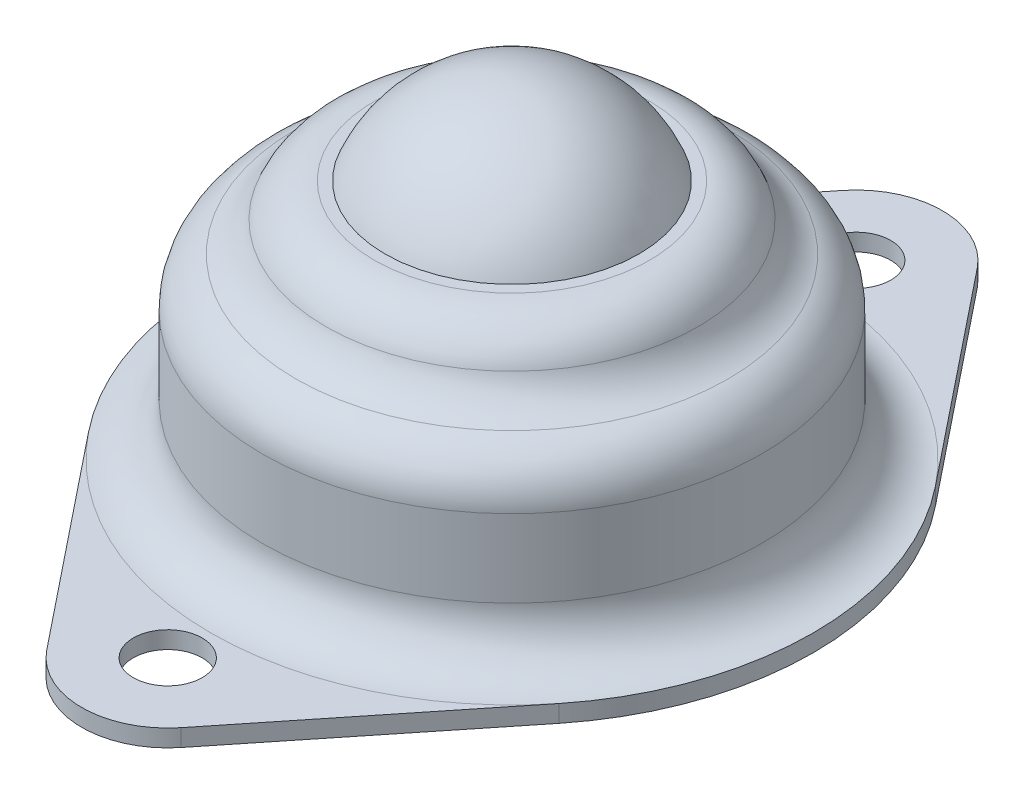
SolidWorks part; units mm, degrees
ref_plane "前视基准面" through (0, 0, 0) normal (0, 0, 1) x (1, 0, 0)
ref_plane "上视基准面" through (0, 0, 0) normal (0, 1, 0) x (1, 0, 0)
ref_plane "右视基准面" through (0, 0, 0) normal (1, 0, 0) x (0, 0, -1)
other "Configuration Table"
sketch "草图1" plane through (0, 0, 0) normal (0, 1, 0) x (1, 0, 0)
  line L0 (0, 0) -> (17.5, 0) construction
  line L1 (0, 25) -> (0, -25) construction
  line L2 (-3.9031, 23.125) -> (-13.6609, 10.9375)
  line L3 (3.9031, 23.125) -> (13.6609, 10.9375)
  line L4 (0, 0) -> (-17.5, 0) construction
  line L5 (3.9031, -23.125) -> (13.6609, -10.9375)
  line L6 (-3.9031, -23.125) -> (-13.6609, -10.9375)
  arc A1 (-13.6609, 10.9375) -> (-13.6609, -10.9375) centre (0, 0) ccw
  circle A2 centre (0, 20) radius 2
  arc A4 (3.9031, 23.125) -> (-3.9031, 23.125) centre (0, 20) ccw
  circle A6 centre (0, -20) radius 2
  arc A7 (13.6609, -10.9375) -> (13.6609, 10.9375) centre (0, 0) ccw
  arc A8 (3.9031, -23.125) -> (-3.9031, -23.125) centre (0, -20) cw
  point P15 (0, 0)
  dimension "D1" = 4
  dimension "D4" = 50
  dimension "D2" = 40
  dimension "D3" = 35
extrude "凸台-拉伸1" add sketch "草图1" along normal blind 1
sketch "草图3" plane through (0, 0, 0) normal (1, 0, 0) x (0, 0, -1)
  line L0 (0, 0) -> (0, 20) construction
  line L1 (-14.5, 1) -> (-14.5, 8.5)
  line L2 (-23.125, 1) -> (-10.9375, 1) construction
  line L5 (-8, 15) -> (0, 15)
  line L6 (0, 15) -> (0, 1)
  line L7 (10.9375, 1) -> (-10.9375, 1) construction
  line L8 (0, 1) -> (-14.5, 1)
  line L13 (-14.5, 8.5) -> (-8, 15) construction
  line L14 (0, 20) -> (0, 15)
  arc A1 (0, 20) -> (0, 4.12) centre (0, 12.06) ccw
  arc A2 (-14.5, 8.5) -> (-12.5575, 11.3075) centre (-11.5, 8.5) cw
  arc A3 (-12.5575, 11.3075) -> (-10.8075, 13.0575) centre (-13.6149, 14.1149) ccw
  arc A4 (-10.8075, 13.0575) -> (-8, 15) centre (-8, 12) cw
  dimension "D4" = 15.88
  dimension "D5" = 3
  dimension "D1" = 20
  dimension "D2" = 29
  dimension "D3" = 5
  dimension "D6" = 45
  dimension "D7" = 16
revolve "旋转2" add sketch "草图3" angle 360 about L6 region at (0, 5.9194, 8.8595) region at (0, 10.2105, 3.5304) region at (0, 17.0662, 2.9352)
fillet "圆角1" radius 3 1 edges at (0, 1, 14.5)
equation "\"фa\"= 4mm"
equation "\"p\"= 40mm"
equation "\"b\"= 35mm"
equation "\"d\"= 15.88mm"
equation "\"D1\"= 29mm"
equation "\"DD\"= 50mm"
equation "\"h\"= 5mm"
equation "\"h1\"= 1mm"
equation "\"HH\"= 20mm"
equation "\"D1@草图1\"=\"фa\""
equation "\"D4@草图1\"=\"DD\""
equation "\"D2@草图1\"=\"p\""
equation "\"D3@草图1\"=\"b\""
equation "\"D1@凸台-拉伸1\"=\"h1\""
equation "\"D1@草图3\"= \"HH\""
equation "\"D2@草图3\"=\"D1\""
equation "\"D3@草图3\"=\"h\""
equation "\"D4@草图3\"=\"d\""
